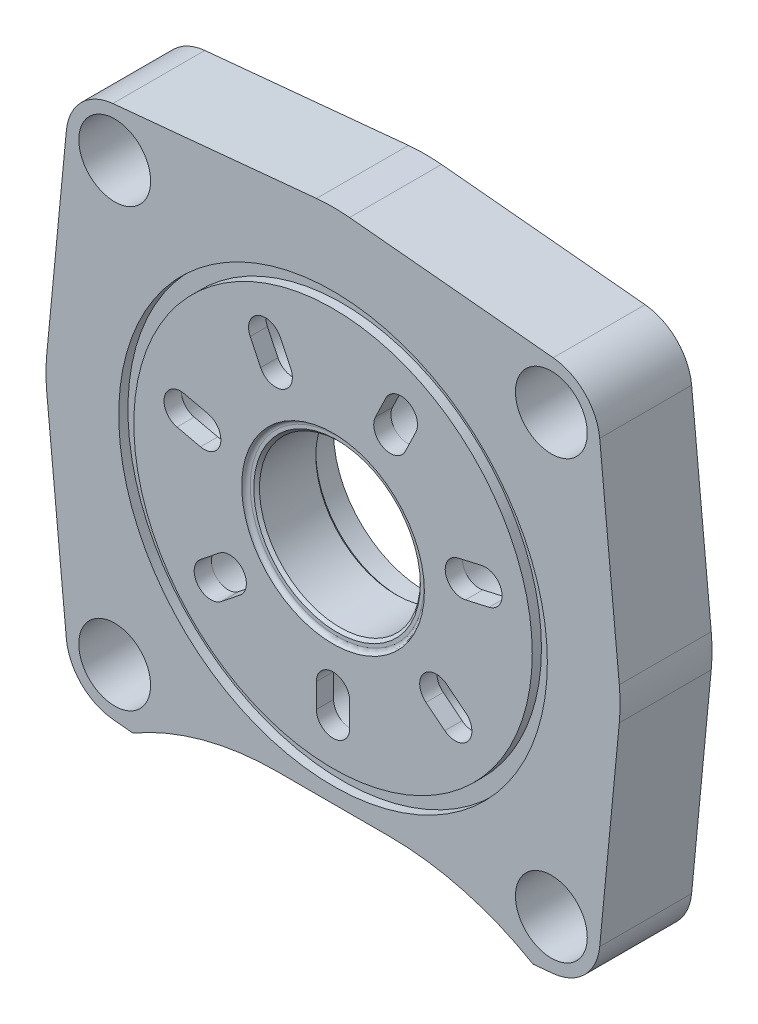
SolidWorks part; units mm, degrees
ref_plane "Front Plane" through (0, 0, 0) normal (0, 0, 1) x (1, 0, 0)
ref_plane "Top Plane" through (0, 0, 0) normal (0, 1, 0) x (1, 0, 0)
ref_plane "Right Plane" through (0, 0, 0) normal (1, 0, 0) x (0, 0, -1)
sketch "Sketch1" plane through (0, 0, 0) normal (0, 0, 1) x (1, 0, 0)
  line L0 (-54.025, 0) -> (0, 0) construction
  line L1 (0, 0) -> (0, 55.5456) construction
  line L2 (0, 50.1) -> (-38.3148, 46.4107)
  line L3 (-46.4107, 38.3148) -> (-50.1, 0)
  line L4 (0, 50.1) -> (38.3148, 46.4107)
  line L5 (46.4107, 38.3148) -> (50.1, 0)
  line L6 (46.4107, -38.3148) -> (50.1, 0)
  line L7 (0, -50.1) -> (38.3148, -46.4107)
  line L8 (0, -50.1) -> (-38.3148, -46.4107)
  line L9 (-46.4107, -38.3148) -> (-50.1, 0)
  line L10 (0, -23) -> (0, -27.2) construction
  line L11 (2.9, -23) -> (2.9, -27.2)
  line L12 (-2.9, -23) -> (-2.9, -27.2)
  line L13 (-17.9821, -14.3403) -> (-21.2658, -16.9589) construction
  line L14 (-16.174, -16.6076) -> (-19.4577, -19.2262)
  line L15 (-19.7902, -12.073) -> (-23.0739, -14.6916)
  line L16 (-22.4233, 5.118) -> (-26.518, 6.0526) construction
  line L17 (-23.0687, 2.2907) -> (-27.1633, 3.2253)
  line L18 (-21.778, 7.9453) -> (-25.8727, 8.8799)
  line L19 (-9.9793, 20.7223) -> (-11.8016, 24.5064) construction
  line L20 (-12.5921, 19.464) -> (-14.4144, 23.2481)
  line L21 (-7.3665, 21.9805) -> (-9.1888, 25.7646)
  line L22 (9.9793, 20.7223) -> (11.8016, 24.5064) construction
  line L23 (7.3665, 21.9805) -> (9.1888, 25.7646)
  line L24 (12.5921, 19.464) -> (14.4144, 23.2481)
  line L25 (22.4233, 5.118) -> (26.518, 6.0526) construction
  line L26 (21.778, 7.9453) -> (25.8727, 8.8799)
  line L27 (23.0687, 2.2907) -> (27.1633, 3.2253)
  line L28 (17.9821, -14.3403) -> (21.2658, -16.9589) construction
  line L29 (19.7902, -12.073) -> (23.0739, -14.6916)
  line L30 (16.174, -16.6076) -> (19.4577, -19.2262)
  line L31 (0, 0) -> (0, -76.0632) construction
  arc A0 (-46.4107, 38.3148) -> (-38.3148, 46.4107) centre (-37.4521, 37.4521) cw
  arc A1 (46.4107, 38.3148) -> (38.3148, 46.4107) centre (37.4521, 37.4521) ccw
  arc A2 (46.4107, -38.3148) -> (38.3148, -46.4107) centre (37.4521, -37.4521) cw
  arc A3 (-46.4107, -38.3148) -> (-38.3148, -46.4107) centre (-37.4521, -37.4521) ccw
  arc A4 (12.2, -47.6) -> (-12.2, -47.6) centre (0, -70.0565) ccw construction
  circle A5 centre (0, 0) radius 14
  arc A6 (26, -47.7253) -> (12.2, -47.6) centre (18.6504, -97.1822) ccw construction
  arc A7 (-12.2, -47.6) -> (-26, -47.7253) centre (-18.6504, -97.1822) ccw construction
  circle A8 centre (-38, 38) radius 6.25
  circle A9 centre (38, 38) radius 6.25
  circle A10 centre (38, -38) radius 6.25
  circle A11 centre (-38, -38) radius 6.25
  arc A12 (2.9, -23) -> (-2.9, -23) centre (0, -23) ccw
  arc A13 (-2.9, -27.2) -> (2.9, -27.2) centre (0, -27.2) ccw
  arc A14 (-16.174, -16.6076) -> (-19.7902, -12.073) centre (-17.9821, -14.3403) ccw
  arc A15 (-23.0739, -14.6916) -> (-19.4577, -19.2262) centre (-21.2658, -16.9589) ccw
  arc A16 (-23.0687, 2.2907) -> (-21.778, 7.9453) centre (-22.4233, 5.118) ccw
  arc A17 (-25.8727, 8.8799) -> (-27.1633, 3.2253) centre (-26.518, 6.0526) ccw
  arc A18 (-12.5921, 19.464) -> (-7.3665, 21.9805) centre (-9.9793, 20.7223) ccw
  arc A19 (-9.1888, 25.7646) -> (-14.4144, 23.2481) centre (-11.8016, 24.5064) ccw
  arc A20 (7.3665, 21.9805) -> (12.5921, 19.464) centre (9.9793, 20.7223) ccw
  arc A21 (14.4144, 23.2481) -> (9.1888, 25.7646) centre (11.8016, 24.5064) ccw
  arc A22 (21.778, 7.9453) -> (23.0687, 2.2907) centre (22.4233, 5.118) ccw
  arc A23 (27.1633, 3.2253) -> (25.8727, 8.8799) centre (26.518, 6.0526) ccw
  arc A24 (19.7902, -12.073) -> (16.174, -16.6076) centre (17.9821, -14.3403) ccw
  arc A25 (19.4577, -19.2262) -> (23.0739, -14.6916) centre (21.2658, -16.9589) ccw
  circle A26 centre (0, 0) radius 23 construction
  circle A27 centre (0, 0) radius 27.2 construction
  point P36 (0, -25.1)
  point P46 (-19.624, -15.6496)
  point P53 (-24.4707, 5.5853)
  point P60 (-10.8905, 22.6143)
  point P67 (10.8905, 22.6143)
  point P74 (24.4707, 5.5853)
  point P81 (19.624, -15.6496)
  point P86 (0, 0)
  dimension "D5" = 9
  dimension "D12" = 50
  dimension "D14" = 28
  dimension "D17" = 12.5
  dimension "D18" = 23
  dimension "D19" = 27.2
  dimension "D22" = 18.6504
  dimension "D15" = 63.5
  dimension "D16" = 63.5
  dimension "D1" = 50.1
  dimension "D2" = 5.5
  dimension "D3" = 50.1
  dimension "D4" = 5.5
  dimension "D6" = 44.5
  dimension "D7" = 12.2
  dimension "D8" = 52
  dimension "D9" = 26
  dimension "D10" = 24.4
  dimension "D11" = 47.6
  dimension "D13" = 5.5
  dimension "D20" = 5.8
  dimension "D21" = 7
extrude "Boss-Extrude1" add sketch "Sketch1" against normal blind 16
sketch "Sketch2" plane through (0, 0, 0) normal (0, 0, 1) x (1, 0, 0)
  circle A0 centre (0, 0) radius 15.9
  dimension "D1" = 31.8
extrude "Cut-Extrude1" cut sketch "Sketch2" against normal blind 0.7
sketch "Sketch3" plane through (0, 0, 0) normal (0, 0, 1) x (1, 0, 0)
  circle A0 centre (0, 0) radius 37.3
  circle A1 centre (0, 0) radius 34.675
  dimension "D1" = 74.6
  dimension "D2" = 2.625
extrude "Cut-Extrude2" cut sketch "Sketch3" against normal blind 1.6
sketch "Sketch8" plane through (0, 0, -16) normal (0, 0, -1) x (-1, 0, 0)
  circle A0 centre (0, 0) radius 15.9
  dimension "D1" = 31.8
extrude "Cut-Extrude4" cut sketch "Sketch8" against normal blind 4.5
sketch "Sketch9" plane through (0, 0, 0) normal (0, 0, 1) x (1, 0, 0)
  line L0 (-9.71, -39.9804) -> (9.71, -39.9804)
  line L2 (-38.3148, -46.4107) -> (0, -50.1) construction
  line L3 (0, -50.1) -> (38.3148, -46.4107) construction
  line L4 (0, -50.1) -> (34.8265, -46.7466)
  line L5 (-34.8265, -46.7466) -> (0, -50.1)
  arc A0 (-9.71, -39.9804) -> (-34.8265, -46.7466) centre (-9.71, -89.9804) ccw
  arc A1 (9.71, -39.9804) -> (34.8265, -46.7466) centre (9.71, -89.9804) cw
  circle A3 centre (0, 0) radius 14 construction
  dimension "D1" = 19.42
  dimension "D4" = 50
  dimension "D2" = 25.9804
  dimension "D3" = 50
extrude "Cut-Extrude5" cut sketch "Sketch9" against normal blind 8.5
sketch "Sketch10" plane through (0, 0, -8.5) normal (0, 0, 1) x (1, 0, 0)
  line L0 (-34.8265, -46.7466) -> (0, -50.1) construction
  line L1 (0, -144.6) -> (0, -44.6) construction
  line L2 (26.5, -144.6) -> (26.5, -44.6) construction
  line L3 (-26.5, -47.5483) -> (0, -50.1)
  line L4 (-26.5, -144.6) -> (-26.5, -44.6) construction
  line L8 (12, -144.6) -> (12, -44.6) construction
  line L9 (-12, -144.6) -> (-12, -44.6) construction
  line L10 (0, -50.1) -> (34.8265, -46.7466) construction
  line L11 (0, -50.1) -> (26.5, -47.5483)
  line L12 (12, -95.3997) -> (-12, -95.3997) construction
  arc A2 (-12.6549, -45.404) -> (12.6549, -45.404) centre (0, -144.6) cw
  arc A6 (-24.766, -47.7153) -> (24.766, -47.7153) centre (0, -144.6) ccw construction
  arc A7 (12.6549, -45.404) -> (-12.6549, -45.404) centre (0, -144.6) ccw construction
  arc A8 (26.5, -47.5483) -> (12.6549, -45.404) centre (12, -95.3997) ccw
  arc A11 (-12.6549, -45.404) -> (-26.5, -47.5483) centre (-12, -95.3997) ccw
  dimension "D1" = 44.6
  dimension "D2" = 200
  dimension "D4" = 26.5
  dimension "D5" = 12
  dimension "D6" = 12
  dimension "D7" = 0
  dimension "D8" = 100
  dimension "D9" = 50
  dimension "D10" = 100
  dimension "D3" = 26.5
extrude "Cut-Extrude6" cut sketch "Sketch10" against normal through all
chamfer "Chamfer1" distance 0.5 angle 45 2 edges at (14, 0, -0.7) (-14, 0, -11.5)
fillet "Fillet1" radius 0.8 2 edges at (-15.9, 0, -11.5) (15.9, 0, -0.7)
fillet "Fillet2" radius 30 3 edges at (50.1, 0, -8) (-50.1, 0, -8) (0, 50.1, -8)
sketch "Sketch11" plane through (0, 0, -16) normal (0, 0, -1) x (-1, 0, 0)
  line L1 (13.0599, 27.1192) -> (8.7211, 18.1095) construction
  line L2 (-13.0599, 27.1192) -> (-8.7211, 18.1095) construction
  line L3 (-29.3453, 6.6979) -> (-19.5961, 4.4727) construction
  line L4 (-23.5331, -18.767) -> (-15.7148, -12.5321) construction
  line L5 (0, -30.1) -> (0, 0) construction
  circle A0 centre (0, 0) radius 25.1 construction
  arc A9 (14.4144, 23.2481) -> (9.1888, 25.7646) centre (11.8016, 24.5064) ccw construction
  arc A10 (7.3665, 21.9805) -> (12.5921, 19.464) centre (9.9793, 20.7223) ccw construction
  arc A11 (-9.1888, 25.7646) -> (-14.4144, 23.2481) centre (-11.8016, 24.5064) ccw construction
  arc A12 (-12.5921, 19.464) -> (-7.3665, 21.9805) centre (-9.9793, 20.7223) ccw construction
  arc A13 (-25.8727, 8.8799) -> (-27.1633, 3.2253) centre (-26.518, 6.0526) ccw construction
  arc A14 (-23.0687, 2.2907) -> (-21.778, 7.9453) centre (-22.4233, 5.118) ccw construction
  arc A15 (-23.0739, -14.6916) -> (-19.4577, -19.2262) centre (-21.2658, -16.9589) ccw construction
  arc A16 (-16.174, -16.6076) -> (-19.7902, -12.073) centre (-17.9821, -14.3403) ccw construction
  arc A17 (-2.9, -27.2) -> (2.9, -27.2) centre (0, -27.2) ccw construction
  circle A18 centre (0, -25.1) radius 5
  dimension "D1" = 50.2
  dimension "D2" = 10
extrude "Cut-Extrude7" cut sketch "Sketch11" against normal blind 13 and the other way through all
pattern_circular "CirPattern1" count 7 every 51.429 about axis through (0, 0, -16) along (0, 0, 1) of "Cut-Extrude7"
chamfer "Chamfer2" distance 1 angle 45 7 edges at (5, -25.1, -16) (-14.624, -15.6496, -16) (-19.4707, 5.5853, -16) (-5.8905, 22.6143, -16) (15.8905, 22.6143, -16) (29.4707, 5.5853, -16) (24.624, -15.6496, -16)
